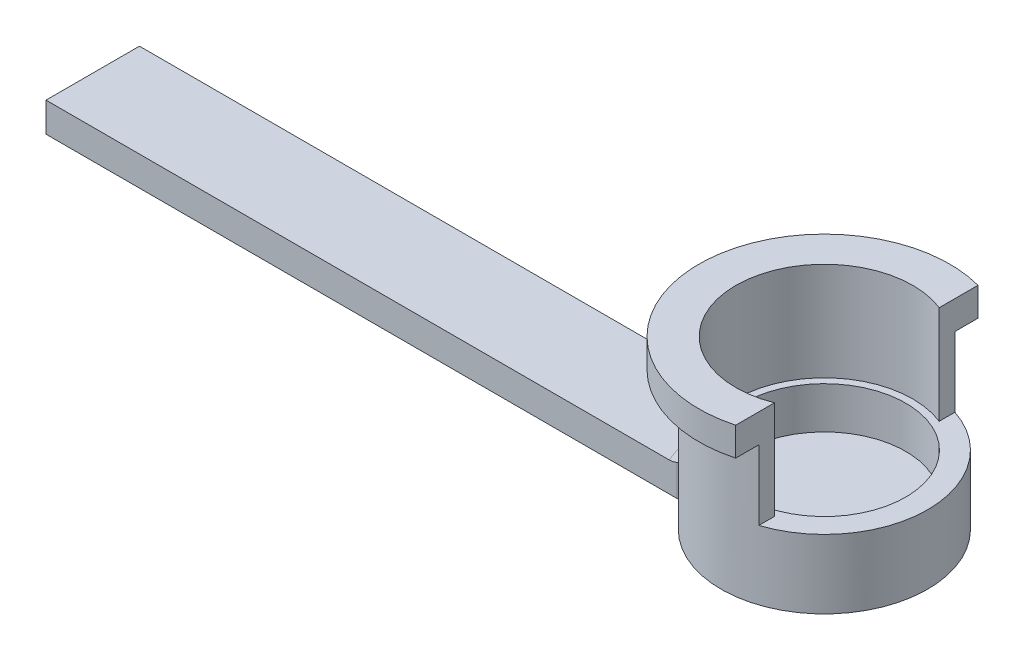
SolidWorks part; units mm, degrees
ref_plane "Front Plane" through (0, 0, 0) normal (0, 0, 1) x (1, 0, 0)
ref_plane "Top Plane" through (0, 0, 0) normal (0, 1, 0) x (1, 0, 0)
ref_plane "Right Plane" through (0, 0, 0) normal (1, 0, 0) x (0, 0, -1)
sketch "0.1mm fit for pot" plane through (0, 0, 0) normal (0, 1, 0) x (1, 0, 0)
  circle A1 centre (0, 0) radius 10.5
  dimension "D2" = 21
extrude "Boss-Extrude1" add sketch "0.1mm fit for pot" along normal blind 2.75
sketch "Sketch4" plane through (0, 2.75, 0) normal (0, 1, 0) x (1, 0, 0)
  circle A0 centre (0, 0) radius 8.275
  circle A1 centre (0, 0) radius 10.5 construction
  circle A2 centre (0, 0) radius 10.5
  dimension "D1" = 16.55
extrude "Boss-Extrude2" add sketch "Sketch4" along normal blind 4.25
sketch "Sketch5" plane through (0, 2.75, 0) normal (0, 1, 0) x (1, 0, 0)
  line L6 (-1, -8.2144) -> (-1, -7.0658)
  line L7 (-1, -7.0658) -> (0.9881, -7.0658)
  line L8 (0.9881, -7.0658) -> (0.9881, -8.2158)
  circle A0 centre (0, 0) radius 8.275 construction
  arc A1 (-1, -8.2144) -> (0.9881, -8.2158) centre (0, 0) ccw
  point P3 (0, -8.25)
  point P6 (0, -8.25)
  point P7 (0, -8.25)
  dimension "D1" = 1.15
extrude "Boss-Extrude3" add sketch "Sketch5" along normal blind 2
fillet "Fillet1" radius 0.25 5 edges at (-1, 4.75, 7.6401) (0.9881, 4.75, 7.6408) (0.9881, 3.75, 7.0658) (-0.006, 4.75, 7.0658) (-1, 3.75, 7.0658)
sketch "Sketch7" plane through (0, 7, 0) normal (0, 1, 0) x (1, 0, 0)
  line L0 (3.2996, 9.9681) -> (3.2996, 8.3733)
  line L1 (3.2996, -8.3733) -> (3.2996, -9.9681)
  arc A0 (3.2996, 9.9681) -> (3.2996, -9.9681) centre (0, 0) ccw
  arc A1 (3.2996, 8.3733) -> (3.2996, -8.3733) centre (0, 0) ccw
  dimension "D1" = 18
  dimension "D2" = 21
extrude "Boss-Extrude6" add sketch "Sketch7" along normal blind 10
sketch "Sketch8" plane through (0, 17, 0) normal (0, 1, 0) x (1, 0, 0)
  line L0 (3.2996, 12.3156) -> (3.2996, 9.9681)
  line L1 (3.2996, -9.9681) -> (3.2996, -12.3156)
  arc A0 (3.2996, 12.3156) -> (3.2996, -12.3156) centre (0, 0) ccw
  arc A1 (3.2996, 9.9681) -> (3.2996, -9.9681) centre (0, 0) ccw construction
  arc A2 (3.2996, 9.9681) -> (3.2996, -9.9681) centre (0, 0) ccw
  dimension "D1" = 2.25
extrude "Boss-Extrude7" add sketch "Sketch8" against normal blind 2.9
sketch "Sketch9" plane through (0, 0, 0) normal (0, -1, 0) x (1, 0, 0)
  line L3 (-9.3642, 4.75) -> (-74.3642, 4.75)
  line L5 (-9.3642, -4.75) -> (-74.3642, -4.75)
  line L6 (-74.3642, 4.75) -> (-74.3642, -4.75)
  circle A0 centre (0, 0) radius 10.5 construction
  arc A1 (-9.3642, 4.75) -> (-9.3642, -4.75) centre (0, 0) ccw
  point P10 (-5.25, 0)
  dimension "D1" = 65
extrude "Boss-Extrude8" add sketch "Sketch9" against normal blind 3
fillet "Fillet2" radius 1.5 3 edges at (-9.3642, 1.5, -4.75) (-9.3642, 1.5, 4.75) (-10.5, 3, 0)
